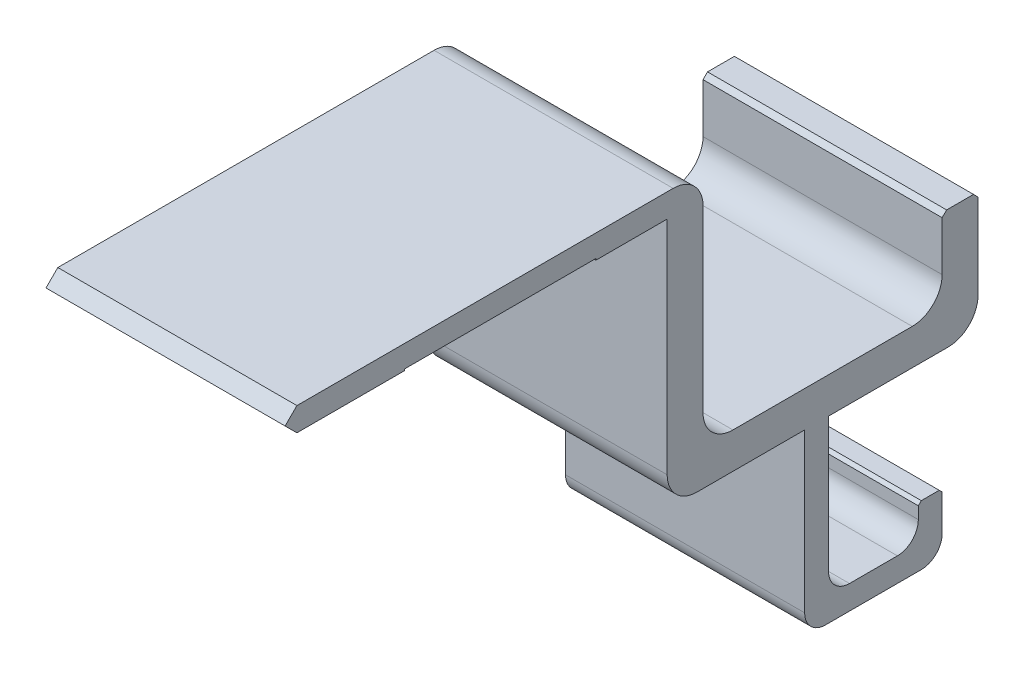
SolidWorks part; units mm, degrees
ref_plane "Front Plane" through (0, 0, 0) normal (0, 0, 1) x (1, 0, 0)
ref_plane "Top Plane" through (0, 0, 0) normal (0, 1, 0) x (1, 0, 0)
ref_plane "Right Plane" through (0, 0, 0) normal (1, 0, 0) x (0, 0, -1)
sketch "Sketch1" plane through (0, 0, 0) normal (1, 0, 0) x (0, 0, -1)
  line L4 (-15, 0) -> (0, 0)
  line L5 (0, 0) -> (0, -40)
  line L6 (0, -40) -> (40, -40)
  line L7 (40, -40) -> (40, -26)
  line L8 (40, -26) -> (46, -26)
  line L9 (46, -26) -> (46, -46)
  line L10 (46, -46) -> (-6, -46)
  line L11 (-6, -46) -> (-6, -3.95)
  line L12 (-6, -3.95) -> (-13.2269, -3.95)
  line L18 (-13.2269, -3.95) -> (-17.9408, -3.95)
  line L19 (-17.9408, -3.95) -> (-17.9408, -3.7)
  line L20 (-17.9408, -3.7) -> (-49.9408, -3.7)
  line L21 (-49.9408, -3.7) -> (-49.9408, -3.95)
  line L22 (-49.9408, -3.95) -> (-69.9408, -3.95)
  line L23 (-69.9408, -3.95) -> (-69.9408, 0)
  line L24 (-69.9408, 0) -> (-15, 0)
  line L25 (17, -46) -> (17, -76)
  line L26 (17, -76) -> (40.0149, -76)
  line L27 (40.0149, -76) -> (40.0149, -66)
  line L28 (40.0149, -66) -> (36.0149, -66)
  line L29 (36.0149, -66) -> (36.0149, -72)
  line L30 (36.0149, -72) -> (21, -72)
  line L31 (21, -72) -> (21, -46)
  point P21 (0, 0)
  point P26 (0, 0)
  point P27 (0, 0)
  dimension "D5" = 3.95
  dimension "D6" = 6
  dimension "D7" = 6
  dimension "D8" = 6
  dimension "D12" = 20
  dimension "D13" = 40
  dimension "D14" = 40
  dimension "D2" = 3.7
  dimension "D3" = 3.95
  dimension "D4" = 32
  dimension "D9" = 4.7263
  dimension "D10" = 4.7139
  dimension "D11" = 7.2269
  dimension "D15" = 20
  dimension "D16" = 4
  dimension "D17" = 4
  dimension "D18" = 4
  dimension "D19" = 23.0149
  dimension "D20" = 30
  dimension "D21" = 20
  dimension "D22" = 25
extrude "Boss-Extrude1" add sketch "Sketch1" along normal mid plane 40 contours L24 L23 L22 L21 L20 L19 L18 L12 L11 L10 L9 L8 L7 L6 L5 L4 | L30 L31 L10 L25 L26 L27 L28 L29 region at (0, -24.3664, 0.2118) region at (0, -59, -20.6219)
fillet "Fillet2" radius 5 1 edges at (0, 0, 0)
fillet "Fillet3" radius 5 2 edges at (0, -40, -40) (0, -40, 0)
fillet "Fillet4" radius 5 2 edges at (0, -46, -46) (0, -46, 6)
fillet "Fillet5" radius 3.5 4 edges at (0, -76, -40.0149) (0, -72, -36.0149) (0, -76, -17) (0, -72, -21)
chamfer "Chamfer1" distance 2 angle 45 2 edges at (0, -3.95, 69.9408) (0, 0, 69.9408)
chamfer "Chamfer2" distance 0.75 angle 45 2 edges at (0, -26, -40) (0, -26, -46)
chamfer "Chamfer3" distance 0.5 angle 45 2 edges at (0, -66, -36.0149) (0, -66, -40.0149)
equation "\"D6@Sketch1\"=6"
equation "\"D7@Sketch1\"=\"D6@Sketch1\""
equation "\"D8@Sketch1\"=\"D6@Sketch1\""
equation "\"D13@Sketch1\"=\"D12@Sketch1\"*2"
equation "\"D17@Sketch1\"=\"D16@Sketch1\""
equation "\"D18@Sketch1\"=\"D16@Sketch1\""
equation "\"D22@Sketch1\"=25"
